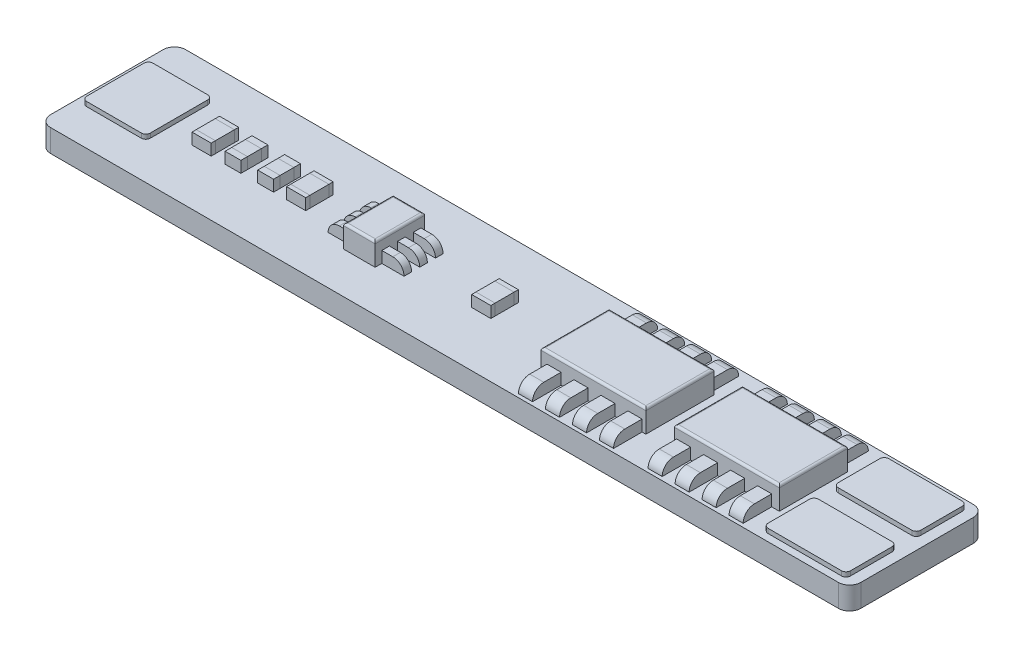
SolidWorks part; units mm, degrees
ref_plane "Front Plane" through (0, 0, 0) normal (0, 0, 1) x (1, 0, 0)
ref_plane "Top Plane" through (0, 0, 0) normal (0, 1, 0) x (1, 0, 0)
ref_plane "Right Plane" through (0, 0, 0) normal (1, 0, 0) x (0, 0, -1)
sketch "Sketch1" plane through (0, 0, 0) normal (0, 1, 0) x (1, 0, 0)
  line L1 (18, -3) -> (-18, -3)
  line L2 (18, -3) -> (18, 3)
  line L3 (18, 3) -> (-18, 3)
  line L4 (-18, -3) -> (-18, 3)
  line L5 (18, -3) -> (-18, 3) construction
  line L6 (18, 3) -> (-18, -3) construction
  point P0 (0, 0)
  dimension "D1" = 36
  dimension "D2" = 6
extrude "Boss-Extrude1" add sketch "Sketch1" along normal mid plane 1
sketch "Sketch2" plane through (0, 0.5, 0) normal (0, 1, 0) x (1, 0, 0)
  line L0 (-18, 3) -> (-18, -3) construction
  line L1 (8.7916, 1.4519) -> (13.4534, 1.4519)
  line L2 (8.7916, 1.4519) -> (8.7916, -1.5746)
  line L3 (8.7916, -1.5746) -> (13.4534, -1.5746)
  line L4 (13.4534, 1.4519) -> (13.4534, -1.5746)
  line L5 (2.8606, 1.4519) -> (7.5224, 1.4519)
  line L6 (2.8606, 1.4519) -> (2.8606, -1.5746)
  line L7 (2.8606, -1.5746) -> (7.5224, -1.5746)
  line L8 (7.5224, 1.4519) -> (7.5224, -1.5746)
  line L9 (-6.3159, 1.0341) -> (-4.9149, 1.0341)
  line L10 (-6.3159, 1.0341) -> (-6.3159, -1.1675)
  line L11 (-6.3159, -1.1675) -> (-4.9149, -1.1675)
  line L12 (-4.9149, 1.0341) -> (-4.9149, -1.1675)
  line L13 (-18, -3) -> (18, -3) construction
  dimension "D1" = 11.6841
  dimension "D2" = 13.0851
  dimension "D3" = 20.8606
  dimension "D4" = 25.5224
  dimension "D5" = 26.7916
  dimension "D6" = 1.4254
  dimension "D7" = 1.8325
  dimension "D8" = 4.0341
  dimension "D9" = 4.4519
extrude "Boss-Extrude2" add sketch "Sketch2" along normal blind 1
sketch "Sketch3" plane through (0, 0.5, 0) normal (0, 1, 0) x (1, 0, 0)
  line L0 (13.4534, 1.4519) -> (8.7916, 1.4519) construction
  line L1 (12.488, 2.7194) -> (13.1135, 2.7194)
  line L2 (12.488, 2.7194) -> (12.488, 1.4519)
  line L3 (12.488, 1.4519) -> (13.1135, 1.4519)
  line L4 (13.1135, 2.7194) -> (13.1135, 1.4519)
  line L5 (-18, 3) -> (-18, -3) construction
  line L6 (-18, -3) -> (18, -3) construction
  line L7 (11.288, 2.7194) -> (11.9135, 2.7194)
  line L8 (11.288, 2.7194) -> (11.288, 1.4519)
  line L9 (11.288, 1.4519) -> (11.9135, 1.4519)
  line L10 (11.9135, 2.7194) -> (11.9135, 1.4519)
  line L11 (10.088, 2.7194) -> (10.7135, 2.7194)
  line L12 (10.088, 2.7194) -> (10.088, 1.4519)
  line L13 (10.088, 1.4519) -> (10.7135, 1.4519)
  line L14 (10.7135, 2.7194) -> (10.7135, 1.4519)
  line L15 (8.888, 2.7194) -> (9.5135, 2.7194)
  line L16 (8.888, 2.7194) -> (8.888, 1.4519)
  line L17 (8.888, 1.4519) -> (9.5135, 1.4519)
  line L18 (9.5135, 2.7194) -> (9.5135, 1.4519)
  line L19 (8.7916, -0.0614) -> (13.4534, -0.0614) construction
  line L20 (8.7916, 1.4519) -> (8.7916, -1.5746) construction
  line L21 (13.4534, -1.5746) -> (13.4534, 1.4519) construction
  line L22 (9.5135, -2.8421) -> (9.5135, -1.5746)
  line L23 (8.888, -1.5746) -> (9.5135, -1.5746)
  line L24 (8.888, -2.8421) -> (8.888, -1.5746)
  line L25 (8.888, -2.8421) -> (9.5135, -2.8421)
  line L26 (10.7135, -2.8421) -> (10.7135, -1.5746)
  line L27 (10.088, -1.5746) -> (10.7135, -1.5746)
  line L28 (10.088, -2.8421) -> (10.088, -1.5746)
  line L29 (10.088, -2.8421) -> (10.7135, -2.8421)
  line L30 (11.9135, -2.8421) -> (11.9135, -1.5746)
  line L31 (11.288, -1.5746) -> (11.9135, -1.5746)
  line L32 (11.288, -2.8421) -> (11.288, -1.5746)
  line L33 (11.288, -2.8421) -> (11.9135, -2.8421)
  line L34 (13.1135, -2.8421) -> (13.1135, -1.5746)
  line L35 (12.488, -1.5746) -> (13.1135, -1.5746)
  line L36 (12.488, -2.8421) -> (12.488, -1.5746)
  line L37 (12.488, -2.8421) -> (13.1135, -2.8421)
  line L38 (7.5224, 1.4519) -> (2.8606, 1.4519) construction
  line L39 (7.3546, 2.7194) -> (6.7291, 2.7194)
  line L40 (7.3546, 2.7194) -> (7.3546, 1.4519)
  line L41 (7.3546, 1.4519) -> (6.7291, 1.4519)
  line L42 (6.7291, 2.7194) -> (6.7291, 1.4519)
  line L43 (6.1546, 2.7194) -> (6.1546, 1.4519)
  line L44 (6.1546, 2.7194) -> (5.5291, 2.7194)
  line L45 (5.5291, 2.7194) -> (5.5291, 1.4519)
  line L46 (6.1546, 1.4519) -> (5.5291, 1.4519)
  line L47 (4.9546, 2.7194) -> (4.9546, 1.4519)
  line L48 (4.9546, 2.7194) -> (4.3291, 2.7194)
  line L49 (4.3291, 2.7194) -> (4.3291, 1.4519)
  line L50 (4.9546, 1.4519) -> (4.3291, 1.4519)
  line L51 (3.7546, 2.7194) -> (3.7546, 1.4519)
  line L52 (3.7546, 2.7194) -> (3.1291, 2.7194)
  line L53 (3.1291, 2.7194) -> (3.1291, 1.4519)
  line L54 (3.7546, 1.4519) -> (3.1291, 1.4519)
  line L55 (2.8606, -0.0614) -> (7.5224, -0.0614) construction
  line L56 (2.8606, 1.4519) -> (2.8606, -1.5746) construction
  line L57 (7.5224, -1.5746) -> (7.5224, 1.4519) construction
  line L58 (3.7546, -1.5746) -> (3.1291, -1.5746)
  line L59 (3.1291, -2.8421) -> (3.1291, -1.5746)
  line L60 (3.7546, -2.8421) -> (3.1291, -2.8421)
  line L61 (3.7546, -2.8421) -> (3.7546, -1.5746)
  line L62 (4.9546, -1.5746) -> (4.3291, -1.5746)
  line L63 (4.3291, -2.8421) -> (4.3291, -1.5746)
  line L64 (4.9546, -2.8421) -> (4.3291, -2.8421)
  line L65 (4.9546, -2.8421) -> (4.9546, -1.5746)
  line L66 (6.1546, -1.5746) -> (5.5291, -1.5746)
  line L67 (5.5291, -2.8421) -> (5.5291, -1.5746)
  line L68 (6.1546, -2.8421) -> (5.5291, -2.8421)
  line L69 (6.1546, -2.8421) -> (6.1546, -1.5746)
  line L70 (6.7291, -2.8421) -> (6.7291, -1.5746)
  line L71 (7.3546, -1.5746) -> (6.7291, -1.5746)
  line L72 (7.3546, -2.8421) -> (7.3546, -1.5746)
  line L73 (7.3546, -2.8421) -> (6.7291, -2.8421)
  line L74 (-4.9149, -1.1675) -> (-4.9149, 1.0341) construction
  line L75 (-4.9149, 0.8659) -> (-3.9279, 0.8659)
  line L76 (-4.9149, 0.8659) -> (-4.9149, 0.5275)
  line L77 (-4.9149, 0.5275) -> (-3.9279, 0.5275)
  line L78 (-3.9279, 0.8659) -> (-3.9279, 0.5275)
  line L79 (-4.9149, -1.1675) -> (-4.9149, 1.0341) construction
  line L80 (-4.9149, 0.1675) -> (-3.9279, 0.1675)
  line L81 (-4.9149, 0.1675) -> (-4.9149, -0.171)
  line L82 (-4.9149, -0.171) -> (-3.9279, -0.171)
  line L83 (-3.9279, 0.1675) -> (-3.9279, -0.171)
  line L84 (-5.6154, 1.0341) -> (-5.6154, -1.1675) construction
  line L85 (-4.9149, -0.531) -> (-3.9279, -0.531)
  line L86 (-4.9149, -0.531) -> (-4.9149, -0.8694)
  line L87 (-4.9149, -0.8694) -> (-3.9279, -0.8694)
  line L88 (-3.9279, -0.531) -> (-3.9279, -0.8694)
  line L89 (-4.9149, 1.0341) -> (-6.3159, 1.0341) construction
  line L90 (-6.3159, -1.1675) -> (-4.9149, -1.1675) construction
  line L91 (-7.3029, -0.531) -> (-7.3029, -0.8694)
  line L92 (-6.3159, -0.8694) -> (-7.3029, -0.8694)
  line L93 (-6.3159, -0.531) -> (-6.3159, -0.8694)
  line L94 (-6.3159, -0.531) -> (-7.3029, -0.531)
  line L95 (-7.3029, 0.1675) -> (-7.3029, -0.171)
  line L96 (-6.3159, -0.171) -> (-7.3029, -0.171)
  line L97 (-6.3159, 0.1675) -> (-6.3159, -0.171)
  line L98 (-6.3159, 0.1675) -> (-7.3029, 0.1675)
  line L99 (-7.3029, 0.8659) -> (-7.3029, 0.5275)
  line L100 (-6.3159, 0.5275) -> (-7.3029, 0.5275)
  line L101 (-6.3159, 0.8659) -> (-6.3159, 0.5275)
  line L102 (-6.3159, 0.8659) -> (-7.3029, 0.8659)
  dimension "D1" = 30.488
  dimension "D2" = 31.1135
  dimension "D3" = 5.7194
  dimension "D6" = 0.36
  dimension "D7" = 0.36
  dimension "D8" = 10.6971
  dimension "D9" = 21.1291
  dimension "D10" = 22.3291
  dimension "D11" = 26.888
  dimension "D12" = 2.1306
  dimension "D13" = 2.469
  dimension "D4" = 4
  dimension "D5" = 4
extrude "Boss-Extrude3" add sketch "Sketch3" along normal blind 0.5
sketch "Sketch4" plane through (13.1135, 0, 0) normal (1, 0, 0) x (0, 0, -1)
  line L0 (-2.8421, 1) -> (-1.5746, 1) construction
  line L1 (-2.8421, 1) -> (-2.8421, 0.5) construction
  line L2 (-2.3421, 1) -> (-2.8421, 1)
  line L3 (-2.8421, 1) -> (-2.8421, 0.5)
  line L4 (-3, 0.5) -> (3, 0.5) construction
  line L5 (-0.0614, 1.5) -> (-0.0614, 0.5) construction
  line L6 (-1.5746, 1.5) -> (1.4519, 1.5) construction
  line L7 (-1.5746, 0.5) -> (1.4519, 0.5) construction
  line L8 (2.7194, 1) -> (2.7194, 0.5)
  line L9 (2.2194, 1) -> (2.7194, 1)
  arc A0 (-2.3421, 1) -> (-2.8421, 0.5) centre (-2.3421, 0.5) ccw
  arc A1 (2.2194, 1) -> (2.7194, 0.5) centre (2.2194, 0.5) cw
extrude "Cut-Extrude1" cut sketch "Sketch4" against normal blind 12.5
fillet "Fillet2" radius 0.5 6 edges at (-3.9279, 1, 0.0018) (-3.9279, 1, -0.6967) (-7.3029, 1, -0.6967) (-7.3029, 1, 0.0018) (-7.3029, 1, 0.7002) (-3.9279, 1, 0.7002)
sketch "Sketch5" plane through (0, 0.5, 0) normal (0, 1, 0) x (1, 0, 0)
  line L0 (18, 0) -> (13.86, 0) construction
  line L1 (14.06, 2.6814) -> (17.3229, 2.6814)
  line L2 (13.86, 2.4814) -> (13.86, 0.6396)
  line L3 (14.06, 0.4396) -> (17.3229, 0.4396)
  line L4 (17.5229, 2.4814) -> (17.5229, 0.6396)
  line L5 (18, -3) -> (18, 3) construction
  line L6 (17.5229, -2.4814) -> (17.5229, -0.6396)
  line L7 (14.06, -0.4396) -> (17.3229, -0.4396)
  line L8 (13.86, -2.4814) -> (13.86, -0.6396)
  line L9 (14.06, -2.6814) -> (17.3229, -2.6814)
  line L10 (2.8606, 1.4519) -> (2.8606, -1.5746) construction
  line L11 (-17.5076, 1.5525) -> (-15.0774, 1.5525)
  line L12 (-17.7076, 1.3525) -> (-17.7076, -1.194)
  line L13 (-17.5076, -1.394) -> (-15.0774, -1.394)
  line L14 (-14.8774, 1.3525) -> (-14.8774, -1.194)
  arc A0 (-15.0774, 1.5525) -> (-14.8774, 1.3525) centre (-15.0774, 1.3525) cw
  arc A1 (-17.7076, -1.194) -> (-17.5076, -1.394) centre (-17.5076, -1.194) ccw
  arc A2 (-15.0774, -1.394) -> (-14.8774, -1.194) centre (-15.0774, -1.194) ccw
  arc A3 (-17.5076, 1.5525) -> (-17.7076, 1.3525) centre (-17.5076, 1.3525) ccw
  arc A4 (13.86, -2.4814) -> (14.06, -2.6814) centre (14.06, -2.4814) ccw
  arc A5 (14.06, -0.4396) -> (13.86, -0.6396) centre (14.06, -0.6396) ccw
  arc A6 (17.5229, -0.6396) -> (17.3229, -0.4396) centre (17.3229, -0.6396) ccw
  arc A7 (17.5229, -2.4814) -> (17.3229, -2.6814) centre (17.3229, -2.4814) cw
  arc A8 (17.3229, 2.6814) -> (17.5229, 2.4814) centre (17.3229, 2.4814) cw
  arc A9 (13.86, 0.6396) -> (14.06, 0.4396) centre (14.06, 0.6396) ccw
  arc A10 (17.3229, 0.4396) -> (17.5229, 0.6396) centre (17.3229, 0.6396) ccw
  arc A11 (14.06, 2.6814) -> (13.86, 2.4814) centre (14.06, 2.4814) ccw
  point P27 (13.86, -2.6814)
  point P30 (13.86, -0.4396)
  point P33 (17.5229, -0.4396)
  point P36 (17.5229, -2.6814)
  point P39 (17.5229, 2.6814)
  point P42 (13.86, 0.4396)
  point P45 (17.5229, 0.4396)
  point P48 (13.86, 2.6814)
  dimension "D1" = 0.2
  dimension "D2" = 10.9994
  dimension "D3" = 14.6623
  dimension "D4" = 17.7381
  dimension "D5" = 20.5682
  dimension "D6" = 0.1005
  dimension "D7" = 1.2295
  dimension "D8" = 1.0123
  dimension "D9" = 2.8459
extrude "Boss-Extrude4" add sketch "Sketch5" along normal blind 0.2
fillet "Fillet3" radius 0.5 4 edges at (18, 0, -3) (18, 0, 3) (-18, 0, -3) (-18, 0, 3)
mirror "Mirror1" about plane through (0, 0, 0) normal (0, 1, 0) of "Boss-Extrude4"
sketch "Sketch6" plane through (0, -0.5, 0) normal (0, -1, 0) x (1, 0, 0)
  line L0 (-8.8078, 1.5383) -> (-6.9246, 1.5383) construction
  line L1 (-8.8078, 2.6648) -> (-6.9246, 2.6648)
  line L2 (-8.8078, 0.4117) -> (-6.9246, 0.4117)
  line L3 (0, 0) -> (-3.8134, 0) construction
  line L4 (-8.8078, -1.5383) -> (-6.9246, -1.5383) construction
  line L5 (-8.8078, -2.6648) -> (-6.9246, -2.6648)
  line L6 (-8.8078, -0.4117) -> (-6.9246, -0.4117)
  line L8 (17.5229, 2.4814) -> (17.5229, 0.6396) construction
  line L9 (14.06, -0.4396) -> (17.3229, -0.4396) construction
  arc A0 (-8.8078, 2.6648) -> (-8.8078, 0.4117) centre (-8.8078, 1.5383) ccw
  arc A1 (-6.9246, 0.4117) -> (-6.9246, 2.6648) centre (-6.9246, 1.5383) ccw
  arc A2 (-8.8078, -2.6648) -> (-8.8078, -0.4117) centre (-8.8078, -1.5383) cw
  arc A3 (-6.9246, -0.4117) -> (-6.9246, -2.6648) centre (-6.9246, -1.5383) cw
  point P2 (-7.8662, 1.5383)
  point P12 (-7.8662, -1.5383)
  dimension "D1" = 1.1266
  dimension "D2" = 24.4475
  dimension "D3" = 25.3891
  dimension "D4" = 1.9779
extrude "Boss-Extrude5" add sketch "Sketch6" along normal up to surface (0.2 mm away) up to face at (-16.2925, -0.7, -0.0792)
fillet "Fillet4" radius 0.1 12 edges at (-5.6154, 1.5, -1.0341) (-4.9149, 1.5, 0.0667) (-5.6154, 1.5, 1.1675) (-6.3159, 1.5, 0.0667) (11.1225, 1.5, -1.4519) (13.4534, 1.5, 0.0614) (11.1225, 1.5, 1.5746) (8.7916, 1.5, 0.0614) (5.1915, 1.5, -1.4519) (7.5224, 1.5, 0.0614) (5.1915, 1.5, 1.5746) (2.8606, 1.5, 0.0614)
sketch "Sketch7" plane through (0, 0.5, 0) normal (0, 1, 0) x (1, 0, 0)
  line L0 (-8.6363, 0.0794) -> (-9.4878, 0.0794) construction
  line L1 (-9.4878, 0.6904) -> (-8.6363, 0.6904)
  line L2 (-9.4878, 0.6904) -> (-9.4878, -0.5316)
  line L3 (-9.4878, -0.5316) -> (-8.6363, -0.5316)
  line L4 (-8.6363, 0.6904) -> (-8.6363, -0.5316)
  line L5 (-9.4878, 0.5014) -> (-8.6363, 0.5014)
  line L6 (-9.4878, 0.5014) -> (-9.4878, -0.3426)
  line L7 (-9.4878, -0.3426) -> (-8.6363, -0.3426)
  line L8 (-8.6363, 0.5014) -> (-8.6363, -0.3426)
  line L9 (-13.6878, 0.5014) -> (-13.6878, -0.3426)
  line L10 (-13.6878, 0.5014) -> (-12.8363, 0.5014)
  line L11 (-12.8363, 0.5014) -> (-12.8363, -0.3426)
  line L12 (-13.6878, -0.3426) -> (-12.8363, -0.3426)
  line L13 (-13.6878, 0.6904) -> (-13.6878, -0.5316)
  line L14 (-13.6878, 0.6904) -> (-12.8363, 0.6904)
  line L15 (-12.8363, 0.6904) -> (-12.8363, -0.5316)
  line L16 (-13.6878, -0.5316) -> (-12.8363, -0.5316)
  line L17 (-0.3734, 0.0435) -> (-1.2249, 0.0435) construction
  line L18 (-1.2249, 0.6545) -> (-0.3734, 0.6545)
  line L19 (-1.2249, 0.6545) -> (-1.2249, -0.5676)
  line L20 (-1.2249, -0.5676) -> (-0.3734, -0.5676)
  line L21 (-0.3734, 0.6545) -> (-0.3734, -0.5676)
  line L22 (-1.2249, 0.4655) -> (-0.3734, 0.4655)
  line L23 (-1.2249, 0.4655) -> (-1.2249, -0.3786)
  line L24 (-1.2249, -0.3786) -> (-0.3734, -0.3786)
  line L25 (-0.3734, 0.4655) -> (-0.3734, -0.3786)
  dimension "D1" = 2
extrude "Boss-Extrude6" add sketch "Sketch7" along normal blind 0.5 contours L24 L19 L20 L21 | L19 L22 L21 L18 | L7 L2 L3 L4 | L2 L5 L4 L1 | L13 L16 L15 L12 | L15 L14 L13 L10 region at (-9.0621, 0.5, -0.5959) region at (-9.0621, 0.5, 0.4371) region at (-13.2621, 0.5, -0.5959) region at (-13.2621, 0.5, 0.4371) region at (-0.7991, 0.5, -0.56) region at (-0.7991, 0.5, 0.4731)
extrude "Boss-Extrude7" add sketch "Sketch7<3>" along normal up to surface (0.5 mm away) separate body contours L19 L24 L21 L22 | L2 L7 L4 L5 | L9 L12 L11 L10 region at (-9.0621, 0.5, -0.0794) region at (-13.2621, 0.5, -0.0794) region at (-0.7991, 0.5, -0.0435) up to face at (-0.7991, 1, -0.56)
sketch "Sketch7<3>" plane through (0, 0.5, 0) normal (0, 1, 0) x (1, 0, 0) same geometry as "Sketch7"
sketch "Sketch8" plane through (0, 0.5, 0) normal (0, 1, 0) x (1, 0, 0)
  line L0 (-10.7657, 0.0641) -> (-10.0625, 0.0641) construction
  line L1 (-10.7657, 0.6619) -> (-10.0625, 0.6619)
  line L2 (-10.7657, 0.6619) -> (-10.7657, -0.5337)
  line L3 (-10.7657, -0.5337) -> (-10.0625, -0.5337)
  line L4 (-10.0625, 0.6619) -> (-10.0625, -0.5337)
  line L5 (-10.7657, 0.3698) -> (-10.0625, 0.3698)
  line L6 (-10.7657, 0.3698) -> (-10.7657, -0.2415)
  line L7 (-10.7657, -0.2415) -> (-10.0625, -0.2415)
  line L8 (-10.0625, 0.3698) -> (-10.0625, -0.2415)
  line L9 (-12.2143, 0.6619) -> (-11.511, 0.6619)
  line L10 (-12.2143, 0.6619) -> (-12.2143, -0.5337)
  line L11 (-11.511, 0.6619) -> (-11.511, -0.5337)
  line L12 (-12.2143, 0.3698) -> (-11.511, 0.3698)
  line L13 (-12.2143, 0.3698) -> (-12.2143, -0.2415)
  line L14 (-12.2143, -0.2415) -> (-11.511, -0.2415)
  line L15 (-11.511, 0.3698) -> (-11.511, -0.2415)
  line L16 (-12.2143, -0.5337) -> (-11.511, -0.5337)
  line L17 (13.4534, -1.5746) -> (13.4534, 1.4519) construction
  dimension "D1" = 23.5159
  dimension "D2" = 24.2192
  dimension "D3" = 24.9644
  dimension "D4" = 1.0409
  dimension "D5" = 1.3331
  dimension "D6" = 1.6387
extrude "Boss-Extrude8" add sketch "Sketch8" along normal up to surface (0.5 mm away) contours L7 L2 L3 L4 | L10 L16 L11 L14 | L10 L12 L11 L9 | L2 L5 L4 L1 region at (-10.4141, 0.5, -0.5158) region at (-10.4141, 0.5, 0.3876) region at (-11.8626, 0.5, -0.5158) region at (-11.8626, 0.5, 0.3876) up to face at (-9.0621, 1, 0.4371)
extrude "Boss-Extrude9" add sketch "Sketch8<3>" along normal up to surface (0.5 mm away) separate body contours L10 L14 L11 L12 | L2 L0 L4 L5 | L0 L6 L7 L8 region at (-10.4141, 0.5, -0.2169) region at (-10.4141, 0.5, 0.0887) region at (-11.8626, 0.5, -0.0641) up to face at (-10.4141, 1, -0.5158)
sketch "Sketch8<3>" plane through (0, 0.5, 0) normal (0, 1, 0) x (1, 0, 0) same geometry as "Sketch8"
